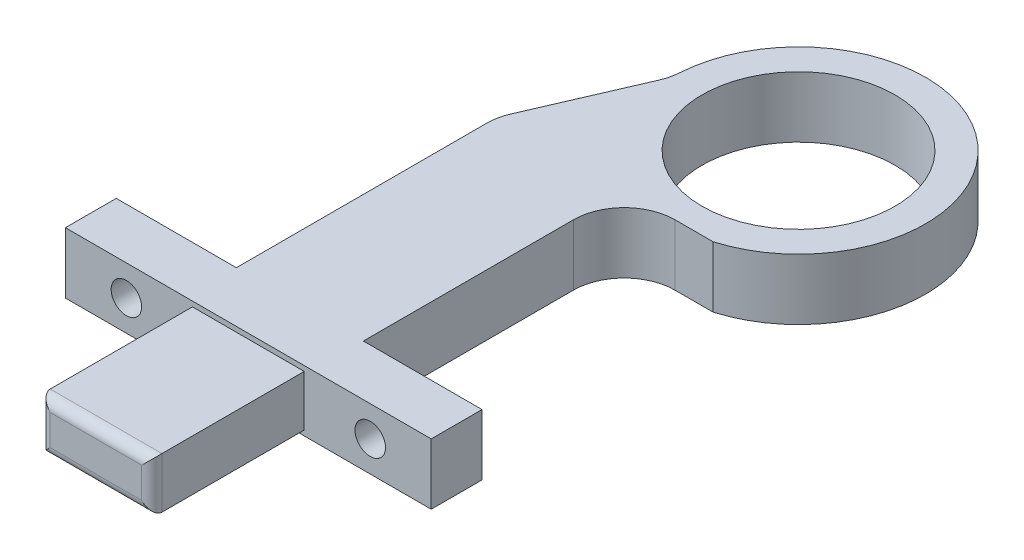
SolidWorks part; units mm, degrees
ref_plane "Alzado" through (0, 0, 0) normal (0, 0, 1) x (1, 0, 0)
ref_plane "Planta" through (0, 0, 0) normal (0, 1, 0) x (1, 0, 0)
ref_plane "Vista lateral" through (0, 0, 0) normal (1, 0, 0) x (0, 0, -1)
sketch "Croquis1" plane through (0, 0, 0) normal (0, 1, 0) x (1, 0, 0)
  line L0 (-12.5, 0) -> (-53.5222, 0) construction
  line L1 (0, 0) -> (-12.5, 21.6506) construction
  line L2 (-29.7673, 10.6211) -> (-25.3747, 20.7837)
  line L3 (-24, -36) -> (-24, -21) construction
  line L4 (-30.1777, -21) -> (-17.6777, -21)
  line L8 (-29.5, -21) -> (-18.5, -21)
  line L9 (-29.5, -21) -> (-29.5, -36)
  line L10 (-29.5, -36) -> (-18.5, -36)
  line L11 (-18.5, -21) -> (-18.5, -36)
  line L12 (-42, -16) -> (-27, -16) construction
  line L13 (-10.5, -16) -> (-6, -16) construction
  line L14 (-42, -16) -> (-27, -16)
  line L15 (-42, -16) -> (-42, -21)
  line L16 (-42, -21) -> (-30.1777, -21)
  line L18 (-6, -16) -> (-10.5, -16)
  line L19 (-6, -16) -> (-6, -21)
  line L20 (-6, -21) -> (-17.6777, -21)
  line L21 (-17.6777, -16) -> (-30.1777, -16)
  line L22 (-17.6777, -16) -> (-17.6777, 4.6717)
  line L23 (-17.6777, 9.6717) -> (-30.1777, 9.6717)
  line L24 (-30.1777, -16) -> (-30.1777, 8.6374)
  line L25 (-8.9286, 9.6717) -> (-12.6777, 9.6717)
  line L26 (-10.5, -16) -> (-17.6777, -16)
  arc A1 (-8.9286, 9.6717) -> (-24.9745, 22.4484) centre (-12.5, 21.6506) ccw
  circle A2 centre (-12.5, 21.6506) radius 9.5
  arc A6 (-30.1777, 8.6374) -> (-29.7673, 10.6211) centre (-25.1777, 8.6374) cw
  arc A7 (-24.9745, 22.4484) -> (-25.3747, 20.7837) centre (-29.9643, 22.7675) cw
  arc A8 (-17.6777, 4.6717) -> (-12.6777, 9.6717) centre (-12.6777, 4.6717) cw
  point P31 (-25, 21.6506)
  dimension "D3" = 25
  dimension "D4" = 5
  dimension "D5" = 19
  dimension "D6" = 21
  dimension "D1" = 25
  dimension "D2" = 60
  dimension "D7" = 11
  dimension "D8" = 15
  dimension "D9" = 24
  dimension "D10" = 5
  dimension "D11" = 18
  dimension "D12" = 18
extrude "Saliente-Extruir1" add sketch "Croquis1" along normal blind 6 contours A1 L14 L15 L16 L4 L20 L19 L18 A2 | L11 L4 L9 L10 | L22 A8 L25 A1 A7 L2 A6 L24 L14 L21 A2 region at (-19.9799, 0, -7.2348) region at (-24, 0, 18.5) region at (-24, 0, 28.5)
sketch "Croquis2" plane through (0, 0, 21) normal (0, 0, 1) x (1, 0, 0)
  line L0 (-42, 3) -> (-6, 3) construction
  line L1 (-42, 6) -> (-42, 0) construction
  line L2 (-6, 6) -> (-6, 0) construction
  line L3 (-24, 6) -> (-24, 0) construction
  line L4 (-29.5, 6) -> (-18.5, 6) construction
  line L5 (-29.5, 0) -> (-18.5, 0) construction
  circle A0 centre (-36, 3) radius 1.5
  circle A1 centre (-12, 3) radius 1.5
  dimension "D3" = 3
  dimension "D4" = 3
  dimension "D1" = 12
  dimension "D2" = 12
extrude "Cortar-Extruir1" cut sketch "Croquis2" against normal blind 6
sketch "Croquis3" plane through (0, 6, 0) normal (0, 1, 0) x (1, 0, 0)
  line L1 (-18.5, -36) -> (-29.5, -36)
  line L2 (-18.5, -36) -> (-18.5, -21)
  line L3 (-18.5, -21) -> (-29.5, -21)
  line L4 (-29.5, -36) -> (-29.5, -21)
extrude "Cortar-Extruir2" cut sketch "Croquis3" against normal blind 0.5
sketch "Croquis4" plane through (0, 0, 0) normal (0, -1, 0) x (1, 0, 0)
  line L1 (-29.5, 36) -> (-18.5, 36)
  line L2 (-29.5, 36) -> (-29.5, 21)
  line L3 (-29.5, 21) -> (-18.5, 21)
  line L4 (-18.5, 36) -> (-18.5, 21)
extrude "Cortar-Extruir3" cut sketch "Croquis4" against normal blind 0.5
fillet "Redondeo1" radius 1 4 edges at (-29.5, 3, 36) (-24, 5.5, 36) (-18.5, 3, 36) (-24, 0.5, 36)
